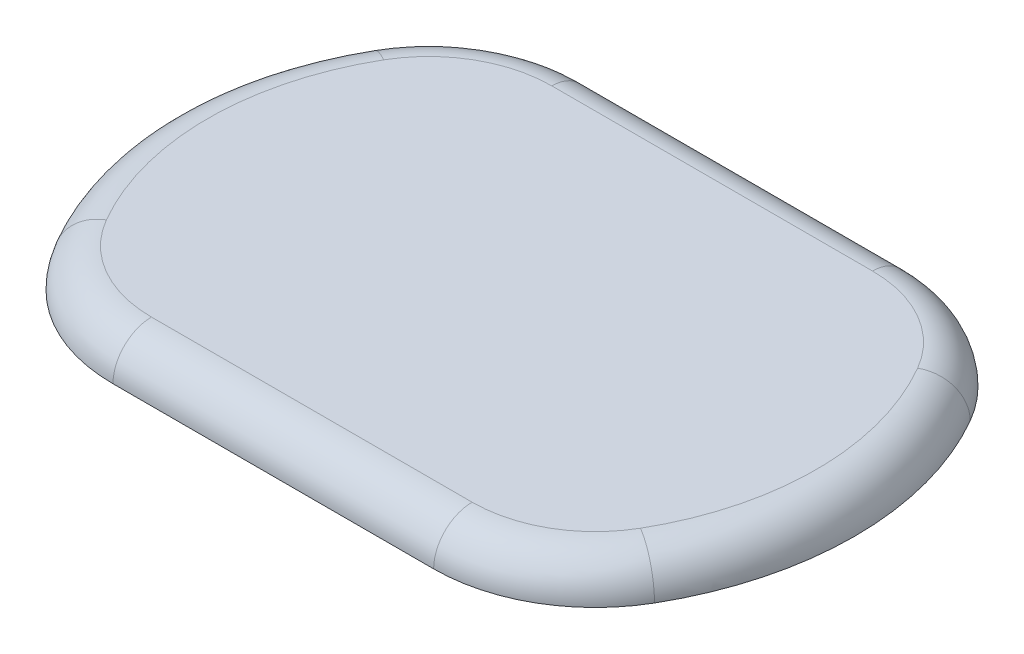
SolidWorks part; units mm, degrees
material "ABS"
ref_plane "前视基准面" through (0, 0, 0) normal (0, 0, 1) x (1, 0, 0)
ref_plane "上视基准面" through (0, 0, 0) normal (0, 1, 0) x (1, 0, 0)
ref_plane "右视基准面" through (0, 0, 0) normal (1, 0, 0) x (0, 0, -1)
sketch "草图1" plane through (0, 0, 0) normal (0, 1, 0) x (1, 0, 0)
  line L0 (-52.2, 20.7111) -> (36.8, 20.7111)
  line L1 (36.8, 20.7111) -> (36.8, -41.2889)
  line L2 (36.8, -41.2889) -> (-52.2, -41.2889)
  line L3 (-52.2, 20.7111) -> (-52.2, -41.2889)
  dimension "D1" = 89
  dimension "D2" = 62
extrude "凸台-拉伸1" add sketch "草图1" along normal blind 5
sketch "草图2" plane through (0, 5, 0) normal (0, 1, 0) x (1, 0, 0)
  line L1 (36.8, 20.7111) -> (-52.2, 20.7111) construction
  line L7 (-28.5205, 20.7111) -> (13.1205, 20.7111)
  line L8 (-52.2, -10.2889) -> (37.4271, -10.2889) construction
  line L9 (-52.2, 20.7111) -> (-52.2, -41.2889) construction
  line L10 (-28.5205, -41.2889) -> (13.1205, -41.2889)
  line L11 (-7.7, 20.7111) -> (-7.7, -51.3025) construction
  line L14 (-68.5146, 33.8822) -> (45.8307, 33.8822)
  line L15 (-68.5146, 33.8822) -> (-68.5146, -48.859)
  line L16 (-68.5146, -48.859) -> (45.8307, -48.859)
  line L17 (45.8307, 33.8822) -> (45.8307, -48.859)
  arc A0 (-46.707, 10.2111) -> (-46.707, -30.7889) centre (-11.2, -10.2889) ccw
  arc A1 (-28.5205, 20.7111) -> (-46.707, 10.2111) centre (-28.5205, -0.2889) ccw
  arc A3 (-28.5205, -41.2889) -> (-46.707, -30.7889) centre (-28.5205, -20.2889) cw
  arc A4 (13.1205, -41.2889) -> (31.307, -30.7889) centre (13.1205, -20.2889) ccw
  arc A5 (31.307, 10.2111) -> (31.307, -30.7889) centre (-4.2, -10.2889) cw
  arc A6 (13.1205, 20.7111) -> (31.307, 10.2111) centre (13.1205, -0.2889) cw
  point P16 (-52.2, -10.2889)
  dimension "D3" = 82
  dimension "D1" = 21
  dimension "D2" = 21
extrude "切除-拉伸2" cut sketch "草图2" against normal up to next
fillet "圆角1" radius 5 8 edges at (36.8, 5, 10.2889) (23.6205, 5, 38.4754) (-7.7, 5, 41.2889) (-39.0205, 5, 38.4754) (-52.2, 5, 10.2889) (-39.0205, 5, -17.8976) (-7.7, 5, -20.7111) (23.6205, 5, -17.8976)
